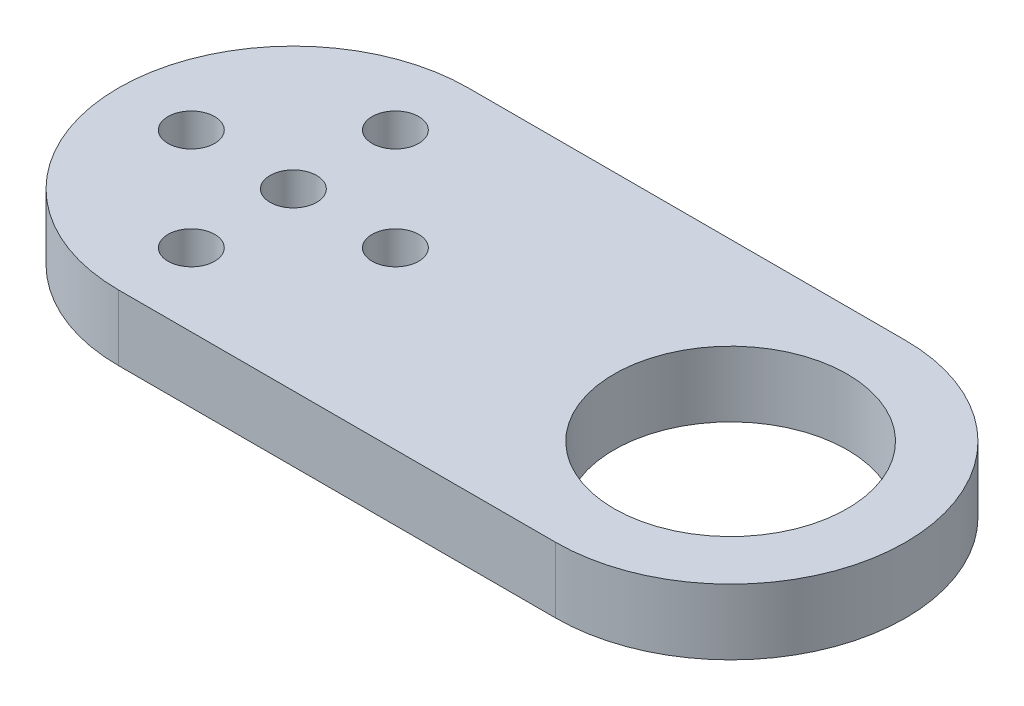
SolidWorks part; units mm, degrees
ref_plane "Front Plane" through (0, 0, 0) normal (0, 0, 1) x (1, 0, 0)
ref_plane "Top Plane" through (0, 0, 0) normal (0, 1, 0) x (1, 0, 0)
ref_plane "Right Plane" through (0, 0, 0) normal (1, 0, 0) x (0, 0, -1)
sketch "Sketch2" plane through (0, 0, 0) normal (0, 1, 0) x (1, 0, 0)
  line L0 (15, 0) -> (-15, 0) construction
  line L1 (15, 12) -> (-15, 12)
  line L2 (15, -12) -> (-15, -12)
  arc A0 (15, 12) -> (15, -12) centre (15, 0) cw
  arc A1 (-15, 12) -> (-15, -12) centre (-15, 0) ccw
  point P4 (0, 0)
  dimension "D1" = 30
  dimension "D2" = 12
  dimension "D3" = 12
extrude "Boss-Extrude1" add sketch "Sketch2" along normal blind 4.5
sketch "Sketch4" plane through (0, 4.5, 0) normal (0, 1, 0) x (1, 0, 0)
  line L0 (-15, 0) -> (-8, 0) construction
  line L1 (15, 0) -> (-15, 0) construction
  line L2 (-15, 0) -> (-8, 0) construction
  circle A0 centre (-15, 0) radius 1.6
  circle A1 centre (-8, 0) radius 1.6
  circle A2 centre (-15, -7) radius 1.6
  circle A3 centre (-22, 0) radius 1.6
  circle A4 centre (-15, 7) radius 1.6
  dimension "D1" = 3.2
  dimension "D2" = 7
  dimension "D3" = 4
extrude "Servo horn holes" cut sketch "Sketch4" against normal through all
sketch "Sketch5" plane through (0, 0, 0) normal (0, -1, 0) x (-1, 0, 0)
  circle A0 centre (-15, 0) radius 8
  dimension "D1" = 16
extrude "Bearing press fit" cut sketch "Sketch5" against normal through all
